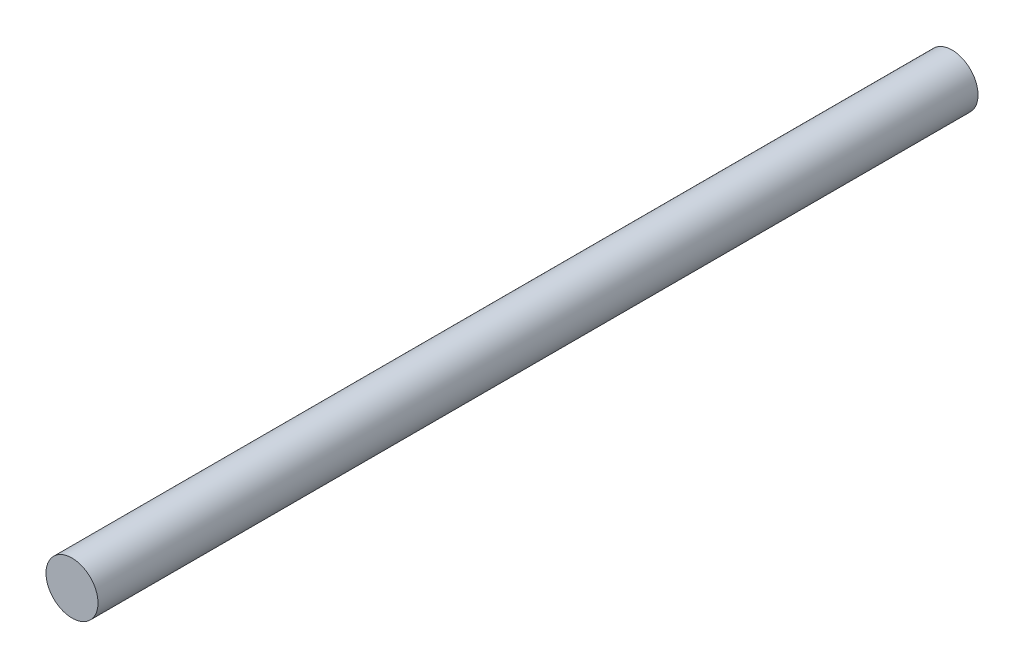
SolidWorks part; units mm, degrees
ref_plane "Front Plane" through (0, 0, 0) normal (0, 0, 1) x (1, 0, 0)
ref_plane "Top Plane" through (0, 0, 0) normal (0, 1, 0) x (1, 0, 0)
ref_plane "Right Plane" through (0, 0, 0) normal (1, 0, 0) x (0, 0, -1)
sketch "Sketch1" plane through (0, 0, 0) normal (0, 0, 1) x (1, 0, 0)
  circle A0 centre (0, 0) radius 6
  dimension "D1" = 12
extrude "Boss-Extrude1" add sketch "Sketch1" along normal mid plane 203
